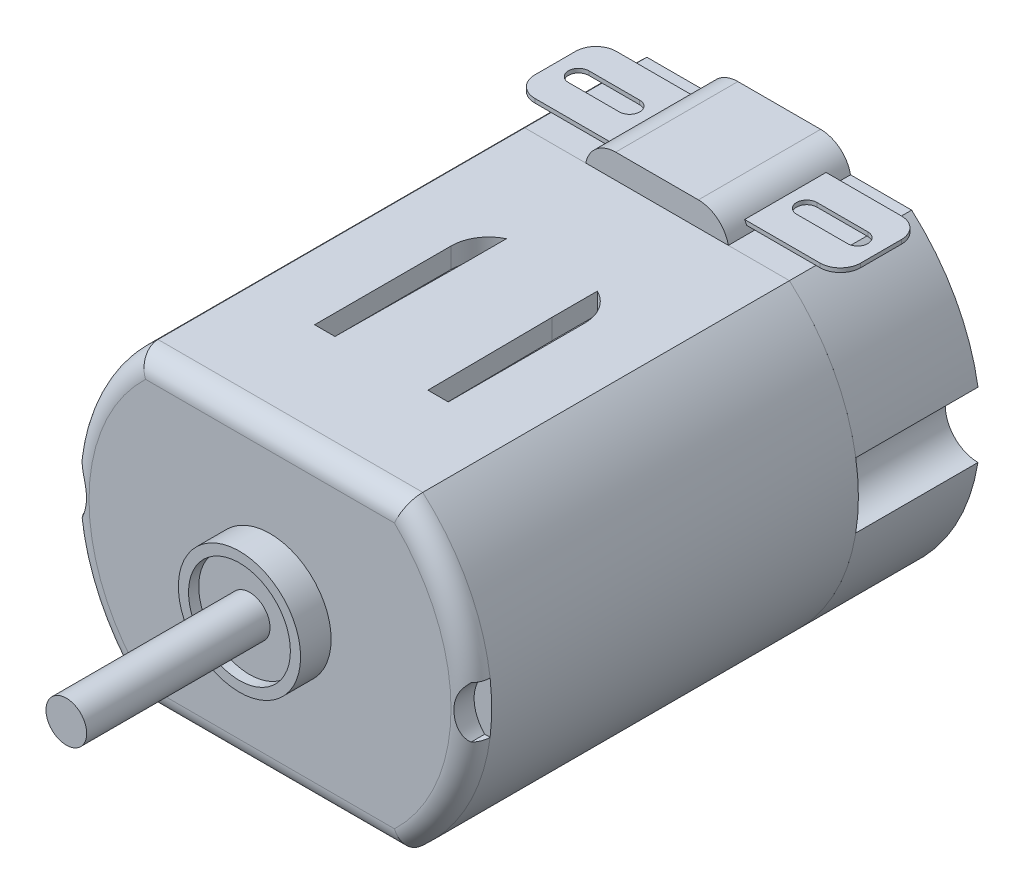
SolidWorks part; units mm, degrees
ref_plane "Ön Düzlem" through (0, 0, 0) normal (0, 0, 1) x (1, 0, 0)
ref_plane "Üst Düzlem" through (0, 0, 0) normal (0, 1, 0) x (1, 0, 0)
ref_plane "Sağ Düzlem" through (0, 0, 0) normal (1, 0, 0) x (0, 0, -1)
sketch "Çizim1" plane through (0, 0, 0) normal (0, 0, 1) x (1, 0, 0)
  line L0 (-6.5, 7.5) -> (6.5, 7.5)
  line L1 (-6.5, -7.5) -> (6.5, -7.5)
  arc A0 (-6.5, 7.5) -> (-6.5, -7.5) centre (0.1144, 0) ccw
  arc A1 (6.5, -7.5) -> (6.5, 7.5) centre (-0.1144, 0) ccw
  point P4 (0, 7.5)
  point P5 (0, -7.5)
  dimension "D5" = 10
  dimension "D6" = 10
  dimension "D1" = 13
  dimension "D2" = 13
  dimension "D3" = 7.5
  dimension "D4" = 7.5
extrude "Yükseklik-Ekstrüzyon1" add sketch "Çizim1" along normal blind 19
fillet "Radyus1" radius 1 4 edges at (-9.8856, 0, 19) (0, -7.5, 19) (9.8856, 0, 19) (0, 7.5, 19)
sketch "Çizim2" plane through (0, 0, 19) normal (0, 0, 1) x (1, 0, 0)
  circle A0 centre (0, 0) radius 3
  dimension "D1" = 6
extrude "Yükseklik-Ekstrüzyon2" add sketch "Çizim2" along normal blind 1.5
sketch "Çizim3" plane through (0, 0, 20.5) normal (0, 0, 1) x (1, 0, 0)
  circle A0 centre (0, 0) radius 2.5
  dimension "D1" = 5
extrude "Kes-Ekstrüzyon1" cut sketch "Çizim3" against normal blind 0.5
sketch "Çizim4" plane through (0, 0, 20) normal (0, 0, 1) x (1, 0, 0)
  circle A0 centre (0, 0) radius 1
  dimension "D1" = 2
extrude "Yükseklik-Ekstrüzyon3" add sketch "Çizim4" along normal blind 9
sketch "Çizim5" plane through (0, 0, 0) normal (0, 0, -1) x (-1, 0, 0)
  line L0 (-6.5, 7.5) -> (6.5, 7.5)
  line L1 (-6.5, -7.5) -> (6.5, -7.5)
  arc A0 (-6.5, -7.5) -> (-6.5, 7.5) centre (0.1144, 0) cw
  arc A1 (6.5, 7.5) -> (6.5, -7.5) centre (-0.1144, 0) cw
extrude "Yükseklik-Ekstrüzyon4" add sketch "Çizim5" along normal blind 6 separate body
sketch "Çizim6" plane through (0, 0, -6) normal (0, 0, -1) x (-1, 0, 0)
  line L0 (0.1144, 5.3474) -> (0.1144, -4.6401) construction
  arc A0 (-9.7568, -1.6) -> (-9.7568, 1.6) centre (-9.7537, 0) ccw
  arc A1 (-6.5, 7.5) -> (-6.5, -7.5) centre (0.1144, 0) ccw construction
  arc A2 (-9.7568, 1.6) -> (-9.7568, -1.6) centre (0.1144, 0) ccw
  arc A3 (9.9855, 1.6) -> (9.9855, -1.6) centre (0.1144, 0) cw
  arc A4 (9.9855, -1.6) -> (9.9855, 1.6) centre (9.9825, 0) cw
  dimension "D1" = 1.6
  dimension "D2" = 10
  dimension "D3" = 9.8681
extrude "Kes-Ekstrüzyon2" cut sketch "Çizim6" against normal blind 6
sketch "Çizim7" plane through (0, 0, -6) normal (0, 0, -1) x (-1, 0, 0)
  circle A0 centre (0, 0) radius 5
  dimension "D1" = 10
extrude "Yükseklik-Ekstrüzyon5" add sketch "Çizim7" along normal blind 2 and the other way blind 2
sketch "Çizim8" plane through (0, 0, -8) normal (0, 0, -1) x (-1, 0, 0)
  circle A0 centre (0, 0) radius 1
  dimension "D1" = 2
extrude "Yükseklik-Ekstrüzyon6" add sketch "Çizim8" along normal blind 1
sketch "Çizim9" plane through (0, 0, -8) normal (0, 0, -1) x (-1, 0, 0)
  line L0 (-3.5707, 3.5) -> (3.5707, 3.5)
  circle A0 centre (0, 0) radius 5 construction
  circle A1 centre (0, 0) radius 5 construction
  arc A2 (-3.5707, 3.5) -> (3.5707, 3.5) centre (0, 0) cw
  dimension "D1" = 5
sketch "Çizim10" plane through (0, 0, -8) normal (0, 0, -1) x (-1, 0, 0)
  line L0 (-2.75, 2.2) -> (2.75, 2.2) construction
  line L1 (-2.75, 2.6) -> (2.75, 2.6)
  line L2 (-2.75, 1.8) -> (2.75, 1.8)
  arc A0 (-2.75, 2.6) -> (-2.75, 1.8) centre (-2.75, 2.2) ccw
  arc A1 (2.75, 1.8) -> (2.75, 2.6) centre (2.75, 2.2) ccw
  point P2 (0, 2.2)
  dimension "D4" = 0.4
  dimension "D1" = 2.2
  dimension "D2" = 5.5
  dimension "D3" = 2.75
extrude "Kes-Ekstrüzyon4" cut sketch "Çizim10" against normal blind 2
extrude "Kes-Ekstrüzyon5" cut sketch "Çizim9" against normal blind 2
sketch "Çizim11" plane through (0, 0, -6) normal (0, 0, -1) x (-1, 0, 0)
  line L0 (6.5, 7.5) -> (-6.5, 7.5) construction
  line L1 (-3.5, 7.5) -> (3.5, 7.5)
  line L2 (-3.5, 7.5) -> (-3.5, 8.7)
  line L3 (-3.5, 8.7) -> (3.5, 8.7)
  line L4 (3.5, 7.5) -> (3.5, 8.7)
  point P6 (0, 7.5)
  dimension "D1" = 1.2
  dimension "D2" = 7
extrude "Yükseklik-Ekstrüzyon7" add sketch "Çizim11" against normal blind 6 separate body
fillet "Radyus6" radius 1.5 2 edges at (-3.5, 8.7, -3) (3.5, 8.7, -3)
sketch "Çizim14" plane through (0, 0, 0) normal (1, 0, 0) x (0, 0, -1)
  line L0 (6, 7.5) -> (6, 8.7) construction
  line L1 (1, 8) -> (5, 8)
  line L2 (1, 8) -> (1, 7.8008)
  line L3 (1, 7.8008) -> (5, 7.8008)
  line L4 (5, 8) -> (5, 7.8008)
  line L5 (0, 8.7) -> (6, 8.7) construction
  dimension "D1" = 4
  dimension "D2" = 1
  dimension "D3" = 0.7
  dimension "D4" = 0.1992
extrude "Yükseklik-Ekstrüzyon9" add sketch "Çizim14" along normal blind 8 and the other way blind 8
sketch "Çizim15" plane through (0, 8.7, 0) normal (0, 1, 0) x (1, 0, 0)
  line L0 (-6.8492, 3) -> (-4.3492, 3) construction
  line L1 (-6.8492, 3.5) -> (-4.3492, 3.5)
  line L2 (-6.8492, 2.5) -> (-4.3492, 2.5)
  line L3 (-3.2992, 1) -> (-3.2992, 5) construction
  line L4 (-8, 5) -> (-3.2992, 5) construction
  line L5 (0, 0) -> (0, 3.8885) construction
  line L6 (6.8492, 3) -> (4.3492, 3) construction
  line L7 (6.8492, 3.5) -> (4.3492, 3.5)
  line L8 (6.8492, 2.5) -> (4.3492, 2.5)
  arc A0 (-6.8492, 3.5) -> (-6.8492, 2.5) centre (-6.8492, 3) ccw
  arc A1 (-4.3492, 2.5) -> (-4.3492, 3.5) centre (-4.3492, 3) ccw
  arc A2 (6.8492, 3.5) -> (6.8492, 2.5) centre (6.8492, 3) cw
  arc A3 (4.3492, 2.5) -> (4.3492, 3.5) centre (4.3492, 3) cw
  point P2 (-5.5992, 3)
  point P16 (5.5992, 3)
  dimension "D1" = 0.5
  dimension "D2" = 2.5
  dimension "D3" = 2.3
  dimension "D4" = 2
extrude "Kes-Ekstrüzyon8" cut sketch "Çizim15" against normal blind 1
fillet "Radyus8" radius 1 4 edges at (-8, 7.9004, -5) (-8, 7.9004, -1) (8, 7.9004, -1) (8, 7.9004, -5)
sketch "Çizim16" plane through (0, 7.5, 0) normal (0, 1, 0) x (1, 0, 0)
  line L0 (-3.2816, -13.5311) -> (-3.2816, -6.8307)
  line L3 (-2.2816, -13.5311) -> (-3.2816, -13.5311)
  line L4 (-2.2297, -5.1651) -> (-2.2297, -7.3924)
  line L5 (-2.2297, -7.3924) -> (-2.2816, -13.5311)
  line L6 (0, 4.3714) -> (0, -19) construction
  line L7 (-3, -19) -> (3, -19) construction
  line L8 (2.2816, -13.5311) -> (3.2816, -13.5311)
  line L9 (3.2816, -13.5311) -> (3.2816, -6.8307)
  line L10 (2.2297, -5.1651) -> (2.2297, -7.3924)
  line L11 (2.2297, -7.3924) -> (2.2816, -13.5311)
  arc A0 (-3.2816, -6.8307) -> (-2.2297, -5.1651) centre (-1.437, -6.8307) cw
  arc A1 (3.2816, -6.8307) -> (2.2297, -5.1651) centre (1.437, -6.8307) ccw
  dimension "D1" = 1
extrude "Kes-Ekstrüzyon9" cut sketch "Çizim16" against normal blind 1
sketch "Çizim17" plane through (0, 0, 19) normal (0, 0, 1) x (1, 0, 0)
  line L0 (-9.5417, 1.2622) -> (-10.2365, 1.2622)
  line L1 (-10.2365, 1.2622) -> (-10.2365, -1.2622)
  line L2 (-10.2365, -1.2622) -> (-9.5417, -1.2622)
  line L3 (0, 4.6529) -> (0, -4.2867) construction
  line L4 (10.2365, -1.2622) -> (9.5417, -1.2622)
  line L5 (10.2365, 1.2622) -> (10.2365, -1.2622)
  line L6 (9.5417, 1.2622) -> (10.2365, 1.2622)
  arc A0 (-9.5417, 1.2622) -> (-9.5417, -1.2622) centre (-10.8039, 0) cw
  arc A1 (9.5417, 1.2622) -> (9.5417, -1.2622) centre (10.8039, 0) ccw
extrude "Kes-Ekstrüzyon10" cut sketch "Çizim17" against normal blind 1
